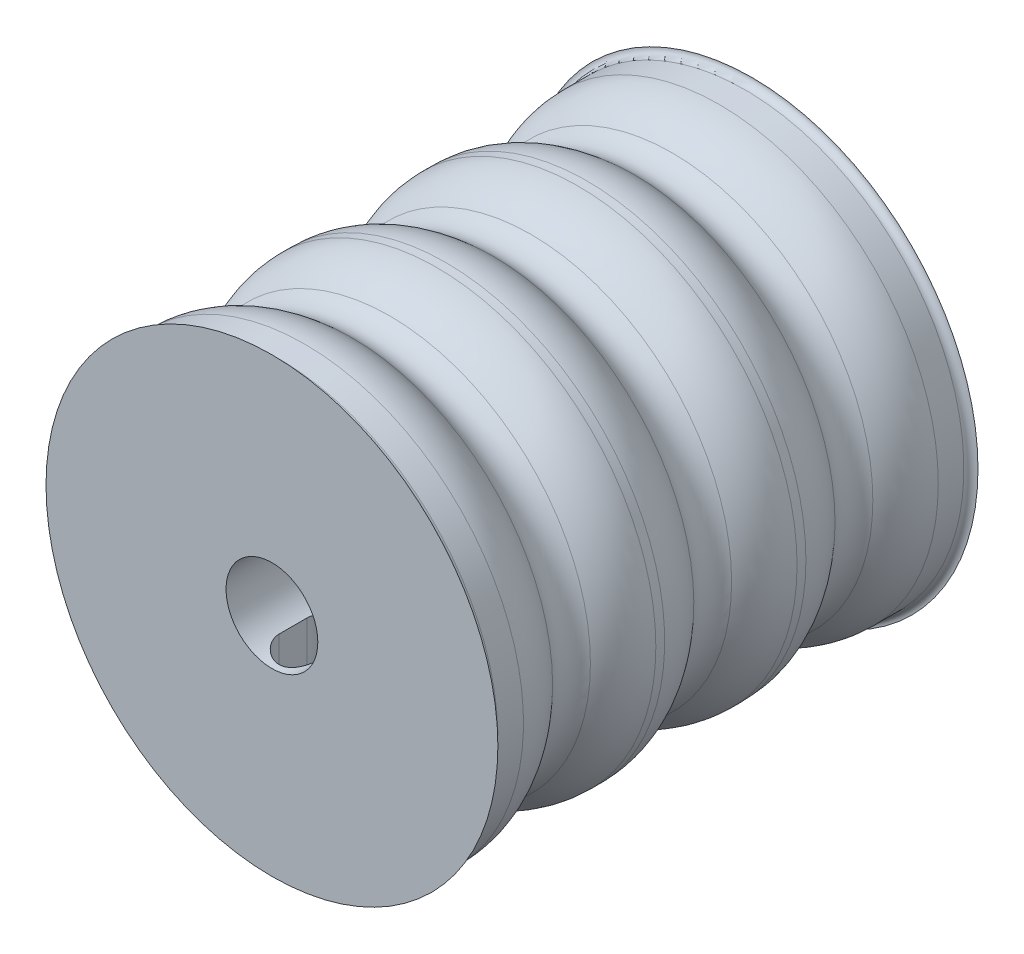
SolidWorks part; units mm, degrees
ref_plane "Plan de face" through (0, 0, 0) normal (0, 0, 1) x (1, 0, 0)
ref_plane "Plan de dessus" through (0, 0, 0) normal (0, 1, 0) x (1, 0, 0)
ref_plane "Plan de droite" through (0, 0, 0) normal (1, 0, 0) x (0, 0, -1)
sketch "Esquisse1" plane through (0, 0, 0) normal (0, 0, 1) x (1, 0, 0)
  circle A0 centre (0, 0) radius 3.25
  circle A1 centre (0, 0) radius 16.5
  dimension "D1" = 33
  dimension "D2" = 6.5
extrude "Boss.-Extru.1" add sketch "Esquisse1" along normal blind 34
sketch "Esquisse9" plane through (0, 0, 34) normal (0, 0, 1) x (1, 0, 0)
  line L0 (0, 0) -> (0, 26.2117) construction
  line L1 (11.35, -6.5529) -> (11.35, 6.5529)
  line L2 (11.35, 6.5529) -> (0, 13.1059)
  line L3 (0, 13.1059) -> (-11.35, 6.5529)
  line L4 (-11.35, 6.5529) -> (-11.35, -6.5529)
  line L5 (-11.35, -6.5529) -> (0, -13.1059)
  line L6 (0, -13.1059) -> (11.35, -6.5529)
  circle A0 centre (0, 0) radius 11.35 construction
  dimension "D1" = 22.7
sketch "Esquisse11" plane through (0, 0, 0) normal (0, 0, -1) x (-1, 0, 0)
  circle A1 centre (-6.9282, 4) radius 2.1
  circle A2 centre (6.9282, 4) radius 2.1
  circle A3 centre (0, -8) radius 2.1
  circle A4 centre (0, 0) radius 8 construction
  dimension "D3" = 4.2
  dimension "D4" = 16
sketch "Esquisse13" plane through (0, 0, 0) normal (0, 1, 0) x (1, 0, 0)
  line L0 (-16.5, -34) -> (-16, -34)
  line L1 (-16.5, -34) -> (16.5, -34) construction
  line L2 (-15.5, -33.5) -> (-15.5, -28.99)
  line L3 (0, 0) -> (0, -49.3031) construction
  line L4 (-15.5, -25.01) -> (-15.5, -18.99)
  line L5 (-16.5, 0) -> (-16.5, -34) construction
  line L6 (-15.5, -15.01) -> (-15.5, -8.99)
  line L7 (-16.5, -17) -> (16.5, -17) construction
  line L8 (-15.5, -5.01) -> (-15.5, -0.5)
  line L9 (-16.5, 0) -> (16.5, 0) construction
  line L10 (-16, 0) -> (-16.5, 0)
  line L11 (-16.5, 0) -> (-16.5, -34)
  line L12 (16.5, -34) -> (16.5, 0) construction
  line L13 (-15.7, -34) -> (-15.7, 0) construction
  arc A0 (-15.5, -28.99) -> (-15.5, -25.01) centre (-15.7, -27) ccw
  arc A1 (-15.5, -18.99) -> (-15.5, -15.01) centre (-15.7, -17) ccw
  arc A2 (-15.5, -8.99) -> (-15.5, -5.01) centre (-15.7, -7) ccw
  arc A3 (-16, -34) -> (-15.5, -33.5) centre (-16, -33.5) ccw
  arc A4 (-15.5, -0.5) -> (-16, 0) centre (-16, -0.5) ccw
  point P20 (-15.5, -34)
  point P23 (-15.5, 0)
  dimension "D15" = 0.5
  dimension "D7" = 2
  dimension "D3" = 10
  dimension "D4" = 0.2
  dimension "D14" = 1
revolve "Enlèvement de matière-Révolution1" cut sketch "Esquisse13" angle 360 about L3
fillet "Congé1" radius 5 6 edges at (-15.5, 0, 5.01) (-15.5, 0, 8.99) (-15.5, 0, 15.01) (-15.5, 0, 28.99) (-15.5, 0, 25.01) (-15.5, 0, 18.99)
sketch "Esquisse15" plane through (0, 0, 0) normal (0, 1, 0) x (1, 0, 0)
  line L0 (0, -20) -> (0, -24) construction
  line L1 (1.5, -20) -> (1.5, -24)
  line L2 (-1.5, -20) -> (-1.5, -24)
  line L3 (-16, -34) -> (16, -34) construction
  line L7 (0, -30) -> (0, -32) construction
  line L8 (1.5, -30) -> (1.5, -32)
  line L9 (-1.5, -30) -> (-1.5, -32)
  line L10 (0, -6.51) -> (0, -9.479) construction
  line L11 (1.5, -6.51) -> (1.5, -9.479) construction
  line L12 (-1.5, -6.51) -> (-1.5, -9.479) construction
  line L14 (-15.5, -5.01) -> (15.5, -5.01) construction
  line L16 (-15.5, -33.5) -> (15.5, -33.5) construction
  arc A0 (1.5, -20) -> (-1.5, -20) centre (0, -20) ccw
  arc A1 (-1.5, -24) -> (1.5, -24) centre (0, -24) ccw
  arc A2 (1.5, -30) -> (-1.5, -30) centre (0, -30) ccw
  arc A3 (-1.5, -32) -> (1.5, -32) centre (0, -32) ccw
  arc A4 (1.5, -6.51) -> (-1.5, -6.51) centre (0, -6.51) ccw construction
  arc A5 (-1.5, -9.479) -> (1.5, -9.479) centre (0, -9.479) ccw construction
  point P3 (0, -22)
  point P8 (0, -31)
  point P19 (0, -7.9945)
  dimension "D3" = 1.5
  dimension "D1" = 2
  dimension "D2" = 2
  dimension "D4" = 12
extrude "Enlèv. mat.-Extru.13" cut sketch "Esquisse15" against normal through all
